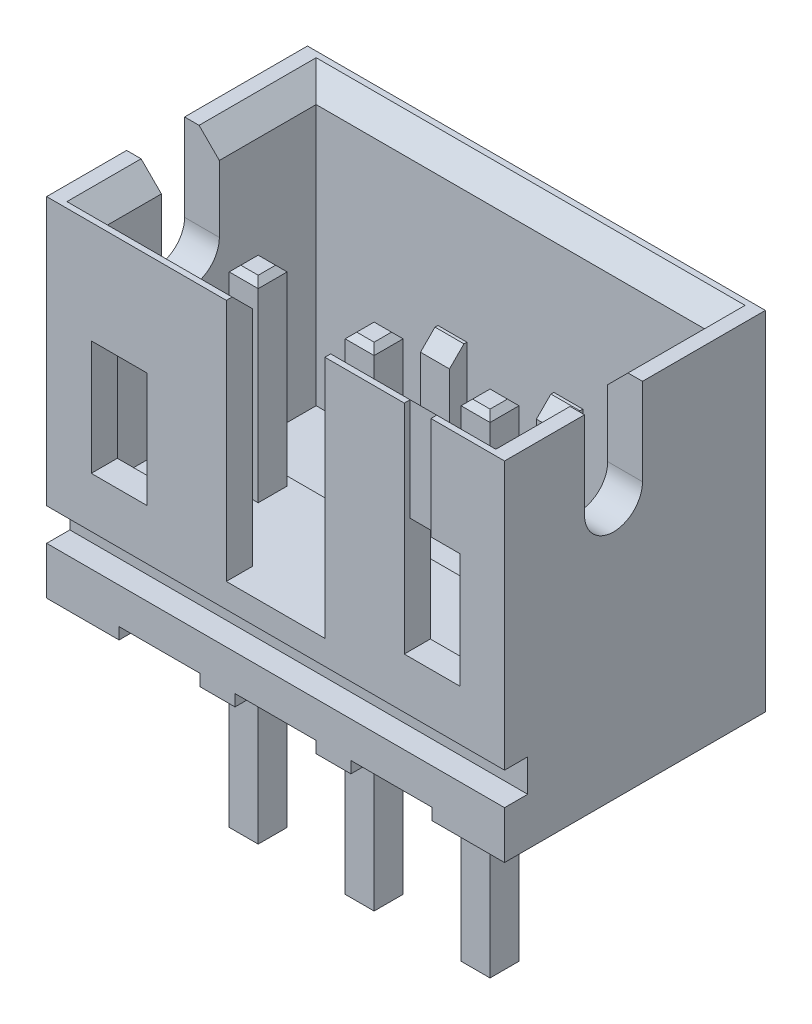
SolidWorks part; units mm, degrees
ref_plane "Спереди" through (0, 0, 0) normal (0, 0, 1) x (1, 0, 0)
ref_plane "Сверху" through (0, 0, 0) normal (0, 1, 0) x (1, 0, 0)
ref_plane "Справа" through (0, 0, 0) normal (1, 0, 0) x (0, 0, -1)
sketch "Body1" plane through (0, 0, 0) normal (0, 1, 0) x (1, 0, 0)
  line L1 (7.9, -4.5) -> (0, -4.5)
  line L2 (7.9, -4.5) -> (7.9, 0)
  line L3 (7.9, 0) -> (0, 0)
  line L4 (0, -4.5) -> (0, 0)
  dimension "depth" = 4.5
  dimension "width" = 7.9
extrude "Бобышка-Вытянуть1" add sketch "Body1" along normal blind 6
sketch "Эскиз2" plane through (0, 6, 0) normal (0, 1, 0) x (1, 0, 0)
  line L0 (7.3, -4.05) -> (7.3, -0.45)
  line L1 (7.3, -0.45) -> (0.6, -0.45)
  line L2 (0.6, -0.45) -> (0.6, -4.05)
  line L3 (0.6, -4.05) -> (7.3, -4.05)
  line L4 (0.6, -0.45) -> (7.3, -4.05) construction
  line L5 (3.95, 0) -> (3.95, -4.5) construction
  line L6 (7.9, 0) -> (0, 0) construction
  line L7 (0, -4.5) -> (7.9, -4.5) construction
  line L12 (0, 0) -> (0, -4.5) construction
  point P16 (3.95, -2.25)
  dimension "D1" = 3.6
  dimension "D2" = 0.6
extrude "Вырез-Вытянуть1" cut sketch "Эскиз2" against normal offset from surface (4.2 mm away) 1.8 up to face at (3.95, 0, 2.25)
sketch "Эскиз3" plane through (0, 0, 4.5) normal (0, 0, 1) x (1, 0, 0)
  line L0 (3.95, 6) -> (3.95, 0) construction
  line L1 (0, 6) -> (7.9, 6) construction
  line L2 (0, 0) -> (7.9, 0) construction
  line L8 (0, 6) -> (0, 0) construction
  line L9 (7.9, 1.38) -> (0, 1.38)
  line L11 (7.9, 0.82) -> (0, 0.82)
  line L12 (0, 1.38) -> (0, 0.82)
  line L13 (7.9, 1.38) -> (7.9, 0.82)
  point P13 (3.95, 0.82)
  point P14 (3.95, 1.38)
  dimension "D1" = 0.82
  dimension "D2" = 0.56
extrude "Вырез-Вытянуть2" cut sketch "Эскиз3" against normal blind 0.4
chamfer "Фаска1" distance 0.35 angle 45 4 edges at (7.3, 6, 2.25) (3.95, 6, 4.05) (0.6, 6, 2.25) (3.95, 6, 0.45)
sketch "Эскиз4" plane through (0, 0, 4.5) normal (0, 0, 1) x (1, 0, 0)
  line L0 (3.95, 1.38) -> (3.95, 0) construction
  line L4 (0, 0) -> (7.9, 0) construction
  line L5 (0, 6) -> (0, 1.38) construction
  line L6 (0.77, 4.23) -> (1.73, 4.23)
  line L7 (0.77, 4.23) -> (0.77, 2.25)
  line L8 (0.77, 2.25) -> (1.73, 2.25)
  line L9 (1.73, 4.23) -> (1.73, 2.25)
  line L10 (7.13, 2.25) -> (6.17, 2.25)
  line L11 (6.17, 4.23) -> (6.17, 2.25)
  line L12 (7.13, 4.23) -> (6.17, 4.23)
  line L13 (7.13, 4.23) -> (7.13, 2.25)
  line L14 (7.9, 1.38) -> (0, 1.38) construction
  dimension "D1" = 0.96
  dimension "D2" = 1.98
  dimension "D3" = 0.77
  dimension "D4" = 2.25
extrude "Вырез-Вытянуть3" cut sketch "Эскиз4" against normal up to next
sketch "Эскиз5" plane through (0, 0, 4.5) normal (0, 0, 1) x (1, 0, 0)
  line L0 (0, 0) -> (7.9, 0) construction
  line L1 (1.25, 0.2) -> (2.65, 0.2)
  line L2 (1.25, 0.2) -> (1.25, 0)
  line L3 (1.25, 0) -> (2.65, 0)
  line L4 (2.65, 0.2) -> (2.65, 0)
  line L6 (3.95, 0.82) -> (3.95, 0) construction
  line L7 (0, 0.82) -> (7.9, 0.82) construction
  line L12 (1.95, 0.82) -> (1.95, 0) construction
  line L13 (0, 0.82) -> (0, 0) construction
  point P14 (1.95, 0.2)
  dimension "D1" = 1.95
  dimension "D2" = 1.4
  dimension "D3" = 0.2
extrude "Вырез-Вытянуть4" cut sketch "Эскиз5" against normal through all
sketch "Эскиз7" plane through (0, 0, 4.5) normal (0, 0, 1) x (1, 0, 0)
  line L0 (0, 6) -> (7.9, 6) construction
  line L1 (6.17, 6) -> (6.63, 6)
  line L2 (6.17, 6) -> (6.17, 4.23)
  line L3 (6.17, 4.23) -> (6.63, 4.23)
  line L4 (6.63, 6) -> (6.63, 4.23)
  line L5 (7.13, 4.23) -> (6.17, 4.23) construction
  line L6 (6.17, 4.23) -> (6.17, 2.25) construction
  dimension "D1" = 0.5
extrude "Вырез-Вытянуть5" cut sketch "Эскиз7" against normal blind 0.1
sketch "Эскиз8" plane through (0, 0, 4.5) normal (0, 0, 1) x (1, 0, 0)
  line L0 (3.95, 0.82) -> (3.95, 1.38) construction
  line L1 (0, 0.82) -> (7.9, 0.82) construction
  line L2 (7.9, 1.38) -> (0, 1.38) construction
  line L3 (3.95, 2.5686) -> (3.95, 0.2176) construction
  line L4 (0, 6) -> (6.17, 6) construction
  line L5 (3.1, 6) -> (4.8, 6)
  line L6 (3.1, 6) -> (3.1, 1.8)
  line L7 (3.1, 1.8) -> (4.8, 1.8)
  line L9 (0, 6) -> (0, 1.38) construction
  line L10 (4.8, 6) -> (4.8, 1.8)
  line L11 (0, 0) -> (1.25, 0) construction
  point P20 (3.95, 6)
  point P21 (3.95, 1.8)
  dimension "D1" = 3.1
  dimension "D2" = 1.8
extrude "Вырез-Вытянуть6" cut sketch "Эскиз8" against normal up to next
sketch "Эскиз9" plane through (0, 0, 0) normal (-1, 0, 0) x (0, 0, 1)
  line L0 (0, 6) -> (4.5, 6) construction
  line L1 (2.12, 6) -> (3.12, 6)
  line L2 (2.12, 6) -> (2.12, 4.5)
  line L3 (2.12, 4.5) -> (3.12, 4.5) construction
  line L4 (3.12, 6) -> (3.12, 4.5)
  line L5 (4.5, 6) -> (4.5, 1.38) construction
  arc A0 (2.12, 4.5) -> (3.12, 4.5) centre (2.62, 4.5) ccw
  point P10 (2.62, 6)
  dimension "D1" = 1
  dimension "D2" = 1.38
  dimension "D3" = 1.5
extrude "Вырез-Вытянуть7" cut sketch "Эскиз9" against normal up to next
ref_plane "Плоскость1" through (3.95, 0, 0) normal (1, 0, 0) x (0, 0, -1)
mirror "Зеркальное отражение1" about plane through (3.95, 0, 0) normal (1, 0, 0) of "Вырез-Вытянуть7"
sketch "Эскиз15" plane through (0, 1.8, 0) normal (0, 1, 0) x (1, 0, 0)
  line L1 (0.6, -0.45) -> (7.3, -0.45)
  line L2 (0.6, -0.45) -> (0.6, -2.4)
  line L3 (0.6, -2.4) -> (7.3, -2.4)
  line L4 (7.3, -0.45) -> (7.3, -2.4)
  line L8 (7.3, -0.45) -> (0.6, -0.45) construction
  line L9 (7.3, -2.12) -> (7.3, -0.45) construction
  line L10 (0.6, -4.05) -> (0.6, -0.45) construction
  line L11 (3.1, -4.05) -> (0.6, -4.05) construction
  dimension "D1" = 1.65
extrude "Вырез-Вытянуть9" cut sketch "Эскиз15" against normal blind 0.65 contours L3 L4 L1 L2
chamfer "Фаска7" distance 0.65 angle 45 1 edges at (3.95, 1.15, 2.4)
sketch "Эскиз10" plane through (0, 0, 0.45) normal (0, 0, 1) x (1, 0, 0)
  line L1 (2.7, 3.4) -> (3.2, 3.4)
  line L2 (2.7, 3.4) -> (2.7, 1.15)
  line L3 (2.7, 1.15) -> (3.2, 1.15)
  line L4 (3.2, 3.4) -> (3.2, 1.15)
  line L5 (2.95, 3.4) -> (2.95, 1.15) construction
  line L6 (0, 6) -> (0, 0) construction
  line L9 (0.6, 1.15) -> (7.3, 1.15) construction
  dimension "D2" = 2.95
  dimension "D3" = 0.25
  dimension "D4" = 2.25
extrude "Бобышка-Вытянуть2" add sketch "Эскиз10" along normal blind 0.3
chamfer "Фаска2" distance 0.25 angle 45 1 edges at (2.95, 3.4, 0.75)
pattern_linear "Линейный массив3" count 2 spacing 2 along (1, 0, 0) of "Бобышка-Вытянуть2", "Фаска2"
sketch "Эскиз12" plane through (0, 0.2, 0) normal (0, -1, 0) x (1, 0, 0)
  line L0 (1.7, 3.05) -> (2.2, 2.55) construction
  line L1 (1.7, 3.05) -> (2.2, 3.05)
  line L2 (1.7, 3.05) -> (1.7, 2.55)
  line L3 (1.7, 2.55) -> (2.2, 2.55)
  line L4 (2.2, 3.05) -> (2.2, 2.55)
  line L5 (2.65, 4.5) -> (1.25, 4.5) construction
  line L6 (0, 0) -> (0, 4.5) construction
  point P4 (1.95, 2.8)
  dimension "D1" = 0.5
  dimension "D2" = 1.7
  dimension "D3" = 1.95
extrude "Бобышка-Вытянуть4" add sketch "Эскиз12" against normal blind 4.9 and the other way blind 3.6
chamfer "Фаска3" distance 0.1 angle 45 4 edges at (1.95, -3.4, 3.05) (2.2, -3.4, 2.8) (1.95, -3.4, 2.55) (1.7, -3.4, 2.8)
chamfer "Фаска4" distance 0.1 angle 45 4 edges at (1.95, 5.1, 2.55) (2.2, 5.1, 2.8) (1.95, 5.1, 3.05) (1.7, 5.1, 2.8)
pattern_linear "Линейный массив2" count 3 spacing 2 along (1, 0, 0) of "Бобышка-Вытянуть4", "Фаска4", "Фаска3", "Вырез-Вытянуть4"
sketch "Эскиз16" plane through (0, 0, 0) normal (0, -1, 0) x (1, 0, 0)
  line L0 (1.7, 3.05) -> (2.2, 2.55) construction
  circle A0 centre (1.95, 2.8) radius 0.05
  point P4 (1.95, 2.8)
  dimension "D1" = 0.1
extrude "Вырез-Вытянуть10" cut sketch "Эскиз16" along normal up to surface (3.4 mm away) up to face at (1.95, -3.4, 2.8)
equation "\"PINS\"= 3'enter the number of pins you need"
equation "\"width@Body1\"= 3.9 + 2.0 * ( \"PINS\" - 1 )"
equation "\"PIN_MASS\"= \"PINS\""
equation "\"D1@Линейный массив2\"=\"PIN_MASS\""
equation "\"GUIDE_MASS\"= \"PINS\" - 1"
equation "\"D1@Линейный массив3\"=\"GUIDE_MASS\""
